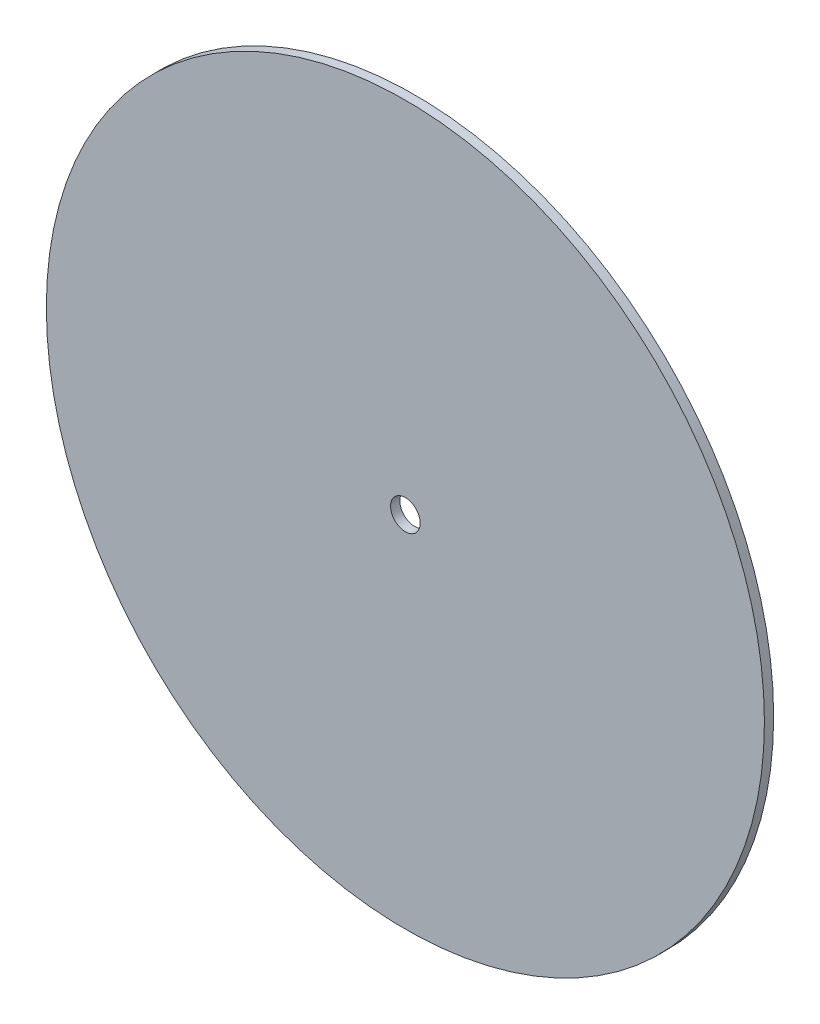
SolidWorks part; units mm, degrees
ref_plane "Front Plane" through (0, 0, 0) normal (0, 0, 1) x (1, 0, 0)
ref_plane "Top Plane" through (0, 0, 0) normal (0, 1, 0) x (1, 0, 0)
ref_plane "Right Plane" through (0, 0, 0) normal (1, 0, 0) x (0, 0, -1)
sketch "Esquisse1" plane through (0, 0, 0) normal (0, 0, 1) x (1, 0, 0)
  circle A0 centre (0, 0) radius 97
  circle A1 centre (0, 0) radius 4
  dimension "D1" = 194
  dimension "D2" = 8
extrude "Boss.-Extru.1" add sketch "Esquisse1" along normal blind 2.5
